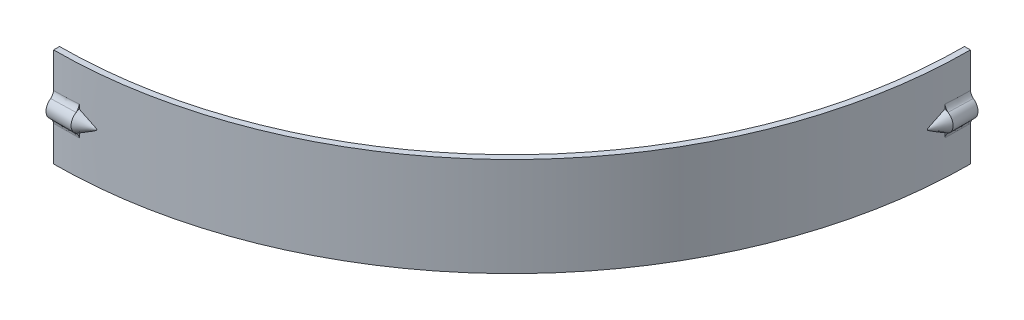
SolidWorks part; units mm, degrees
ref_plane "Front Plane" through (0, 0, 0) normal (0, 0, 1) x (1, 0, 0)
ref_plane "Top Plane" through (0, 0, 0) normal (0, 1, 0) x (1, 0, 0)
ref_plane "Right Plane" through (0, 0, 0) normal (1, 0, 0) x (0, 0, -1)
sketch "Sketch1" plane through (0, 0, 0) normal (0, 0, 1) x (1, 0, 0)
  line L0 (0, 3.3639) -> (0, -36.2756) construction
  line L1 (176.7332, 19.05) -> (174.4472, 19.05)
  line L2 (176.7332, 19.05) -> (176.7332, -19.05)
  line L3 (176.7332, -19.05) -> (174.4472, -19.05)
  line L4 (174.4472, 19.05) -> (174.4472, -19.05)
  line L5 (176.7332, 19.05) -> (174.4472, -19.05) construction
  line L6 (176.7332, -19.05) -> (174.4472, 19.05) construction
  point P0 (175.5902, 0)
  dimension "D1" = 38.1
  dimension "D2" = 2.286
  dimension "D3" = 175.5902
revolve "Revolve1" add sketch "Sketch1" angle 90 about L0
sketch "Sketch4" plane through (0, 0, 0) normal (-1, 0, 0) x (0, 0, 1)
  line L1 (176.7332, 19.05) -> (174.4472, 19.05) construction
  circle A0 centre (175.5902, 0) radius 4.064
  point P5 (175.5902, 19.05)
  dimension "D2" = 8.128
extrude "Boss-Extrude1" add sketch "Sketch4" against normal blind 9.652
sketch "Sketch6" plane through (9.652, 0, 0) normal (1, 0, 0) x (0, 0, -1)
  circle A0 centre (-175.5902, 0) radius 3.175
  circle A2 centre (-175.5902, 0) radius 4.064 construction
  dimension "D1" = 6.35
fillet "Fillet6" radius 2.54 2 edges at (8.128, 3.95, 176.5462) (1.5261, -3.9019, 176.7266)
fillet "Fillet8" radius 2.54 2 edges at (8.128, -3.8394, 174.2577) (1.526, 3.898, 174.4405)
sketch "Sketch7" plane through (0, 0, 0) normal (0, 0, -1) x (-1, 0, 0)
  line L1 (-176.7332, 19.05) -> (-174.4472, 19.05) construction
  circle A0 centre (-175.5902, 0) radius 4.064
  point P7 (-175.5902, 19.05)
  dimension "D1" = 8.128
extrude "Boss-Extrude2" add sketch "Sketch7" against normal blind 9.6012
sketch "Sketch8" plane through (0, 0, 9.6012) normal (0, 0, 1) x (1, 0, 0)
  circle A0 centre (175.5902, 0) radius 3.175
  circle A1 centre (175.5902, 0) radius 4.064 construction
  dimension "D1" = 6.35
fillet "Fillet11" radius 2.54 4 edges at (174.2577, 3.8394, 8.128) (174.441, -3.8981, 1.4752) (176.5462, -3.95, 8.128) (176.727, 3.9018, 1.4752)
sketch "Sketch9" plane through (0, 0, 0) normal (-1, 0, 0) x (0, 0, 1)
  circle A0 centre (175.5902, 0) radius 3.3655
  dimension "D1" = 6.731
extrude "Cut-Extrude1" cut sketch "Sketch9" against normal blind 9.525
sketch "Sketch10" plane through (0, 0, 0) normal (0, 0, -1) x (-1, 0, 0)
  circle A0 centre (-175.5902, 0) radius 3.3655
  dimension "D1" = 6.731
extrude "Cut-Extrude2" cut sketch "Sketch10" against normal blind 9.525
sketch "Sketch11" plane through (0, 0, 0) normal (0, 1, 0) x (1, 0, 0)
  line L0 (9.652, -171.5262) -> (9.652, -175.4632)
  line L1 (9.652, -179.6542) -> (16.4711, -175.7172)
  line L2 (16.4711, -175.4632) -> (9.652, -171.5262)
  line L3 (9.652, -175.5902) -> (13.6215, -175.5902) construction
  line L4 (9.652, -175.4632) -> (16.4711, -175.4632)
  line L5 (16.4711, -175.7172) -> (9.652, -175.7172)
  line L6 (9.652, -175.7172) -> (9.652, -179.6542)
  line L7 (9.652, -178.7652) -> (9.652, -172.4152) construction
  dimension "D1" = 60
  dimension "D2" = 60
  dimension "D3" = 0.254
revolve "Revolve7" add sketch "Sketch11" angle 180 about L3
sketch "Sketch12" plane through (0, 0, 0) normal (0, 1, 0) x (1, 0, 0)
  line L0 (171.5262, -9.6012) -> (175.4632, -16.4203)
  line L1 (175.7172, -16.4203) -> (179.6542, -9.6012)
  line L2 (177.6983, -9.6012) -> (179.6542, -9.6012) construction
  line L3 (179.6542, -9.6012) -> (175.7172, -9.6012)
  line L4 (175.7172, -9.6012) -> (175.7172, -16.4203)
  line L6 (175.4632, -16.4203) -> (175.4632, -9.6012)
  line L7 (175.5902, -9.9069) -> (175.5902, -14.0613) construction
  line L8 (175.4632, -9.6012) -> (171.5262, -9.6012)
  dimension "D1" = 60
  dimension "D2" = 60
  dimension "D3" = 0.254
  dimension "D4" = 0.127
revolve "Revolve8" add sketch "Sketch12" angle 203 about L7
